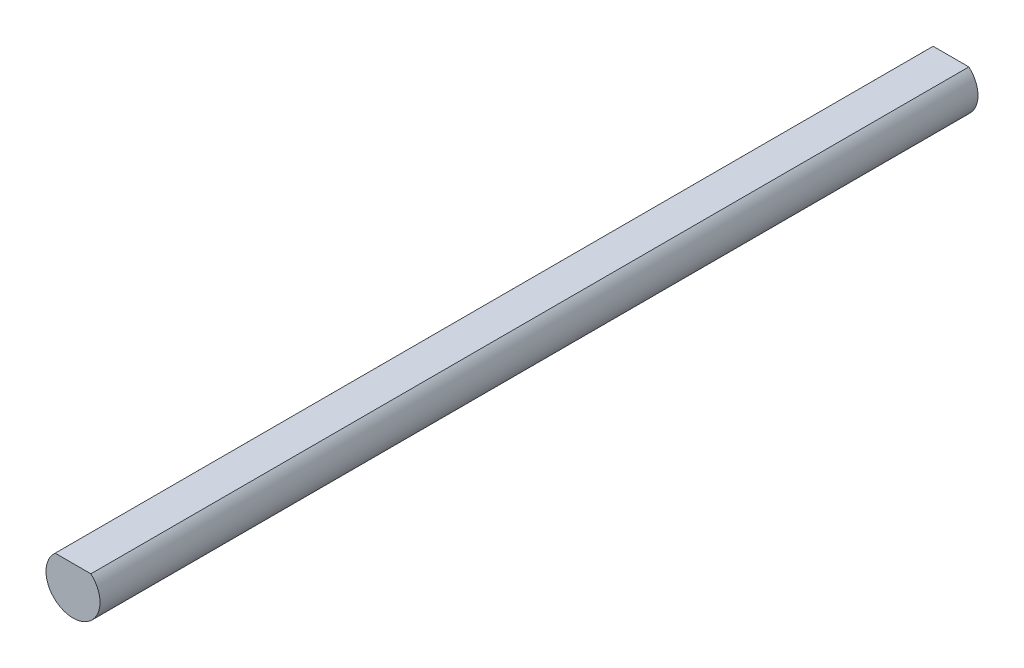
SolidWorks part; units mm, degrees
ref_plane "Front Plane" through (0, 0, 0) normal (0, 0, 1) x (1, 0, 0)
ref_plane "Top Plane" through (0, 0, 0) normal (0, 1, 0) x (1, 0, 0)
ref_plane "Right Plane" through (0, 0, 0) normal (1, 0, 0) x (0, 0, -1)
sketch "Sketch1" plane through (0, 0, 0) normal (0, 0, 1) x (1, 0, 0)
  circle A0 centre (0, 0) radius 4
  dimension "D1" = 8
extrude "Boss-Extrude1" add sketch "Sketch1" along normal blind 130
sketch "Sketch2" plane through (0, 0, 130) normal (0, 0, 1) x (1, 0, 0)
  line L0 (0, 0) -> (0, 3) construction
  line L1 (-2.6458, 3) -> (2.6458, 3)
  circle A0 centre (0, 0) radius 4 construction
  arc A1 (2.6458, 3) -> (-2.6458, 3) centre (0, 0) ccw
  dimension "D1" = 3
extrude "Cut-Extrude1" cut sketch "Sketch2" against normal up to next
